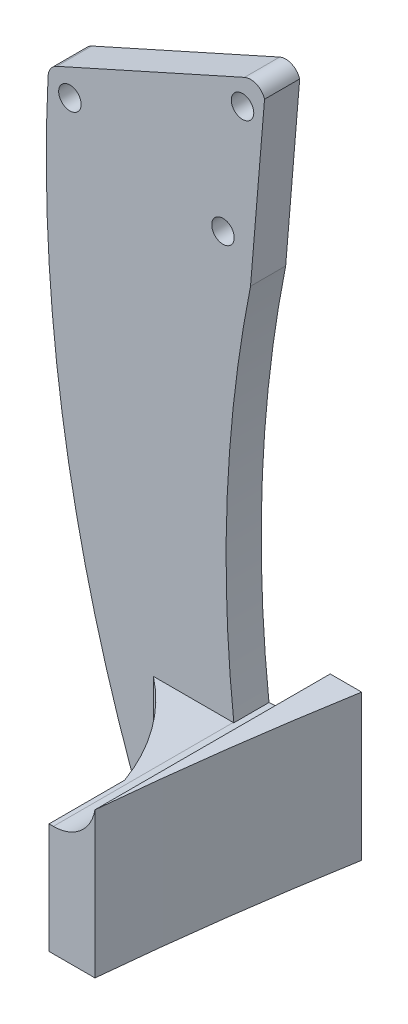
SolidWorks part; units mm, degrees
ref_plane "Front Plane" through (0, 0, 0) normal (0, 0, 1) x (1, 0, 0)
ref_plane "Top Plane" through (0, 0, 0) normal (0, 1, 0) x (1, 0, 0)
ref_plane "Right Plane" through (0, 0, 0) normal (1, 0, 0) x (0, 0, -1)
sketch "Sketch3" plane through (0, 0, 0) normal (0, 0, 1) x (1, 0, 0)
  line L1 (15.3983, 23.3582) -> (42.1037, 35.348)
  line L11 (44.9572, 34.082) -> (42.9625, 10.0438)
  line L12 (40.5893, -44.9338) -> (46.4215, -44.9338)
  line L13 (46.4215, -44.9338) -> (46.4215, -60.6526)
  line L14 (46.4215, -60.6526) -> (28.5746, -60.6526)
  circle A0 centre (17.2652, 20.3952) radius 1.6
  circle A1 centre (41.8252, 31.6252) radius 1.6
  circle A2 centre (39.0452, 14.8552) radius 1.6
  arc A7 (14.1628, 21.5492) -> (26.0473, -58.2164) centre (219.3986, 11.3596) ccw
  arc A9 (15.3983, 23.3582) -> (14.1628, 21.5492) centre (16.2572, 21.4452) ccw
  arc A10 (42.1037, 35.348) -> (44.9572, 34.082) centre (42.9625, 33.435) cw
  arc A11 (42.9625, 10.0438) -> (40.5893, -44.9338) centre (218.6112, -25.0784) ccw
  arc A13 (26.0473, -58.2164) -> (28.5746, -60.6526) centre (29.7797, -56.8733) ccw
  point P5 (40.5893, -45.1561)
  point P19 (0, 0)
  point P20 (29.1285, -60.2007)
  dimension "D1" = 3.2
  dimension "D2" = 3.2
  dimension "D3" = 3.2
  dimension "D8" = 2.097
  dimension "D9" = 2.097
  dimension "D4" = 5.54
  dimension "D5" = 21.78
  dimension "D6" = 11.23
  dimension "D7" = 24.56
extrude "Boss-Extrude2" add sketch "Sketch3" along normal blind 5
sketch "Sketch8" plane through (0, 0, 5) normal (0, 0, 1) x (1, 0, 0)
  line L1 (46.4215, -60.6526) -> (39.8899, -60.6526)
  line L2 (46.4215, -60.6526) -> (46.4215, -44.9338)
  line L3 (46.4215, -44.9338) -> (39.8899, -44.9338)
  line L4 (39.8899, -60.6526) -> (39.8899, -44.9338)
extrude "Boss-Extrude5" add sketch "Sketch8" along normal blind 25.595
sketch "Sketch9" plane through (0, -44.9338, 0) normal (0, 1, 0) x (1, 0, 0)
  line L1 (46.4215, -30.595) -> (46.4215, 0)
  line L2 (46.4215, 0) -> (46.4215, 2.8796)
  line L3 (46.4215, 2.8796) -> (50.8941, 2.8796)
  arc A0 (50.8941, 2.8796) -> (46.4215, -30.595) centre (493.3054, -73.2679) ccw
  point P6 (50.6933, 1.6099)
extrude "Boss-Extrude6" add sketch "Sketch9" against normal blind 15.7253 and the other way blind 5
sketch "Sketch10" plane through (0, -44.9338, 0) normal (0, 1, 0) x (1, 0, 0)
  line L0 (46.4215, -30.595) -> (39.8899, -30.595) construction
  line L1 (42.1037, -5) -> (15.3983, -5) construction
  line L2 (29.147, -5) -> (41.8594, -5)
  line L3 (41.8594, -5) -> (41.8594, -30.595)
  arc A0 (41.8594, -30.595) -> (29.147, -5) centre (8.6942, -31.1128) ccw
  point P3 (29.6336, -5)
  point P9 (41.8594, -27.6629)
  point P10 (0, 0)
  point P11 (0, 0)
extrude "Boss-Extrude7" add sketch "Sketch10" against normal blind 15.7152
fillet "Fillet3" radius 6 1 edges at (46.4215, -44.9338, 15.2975)
